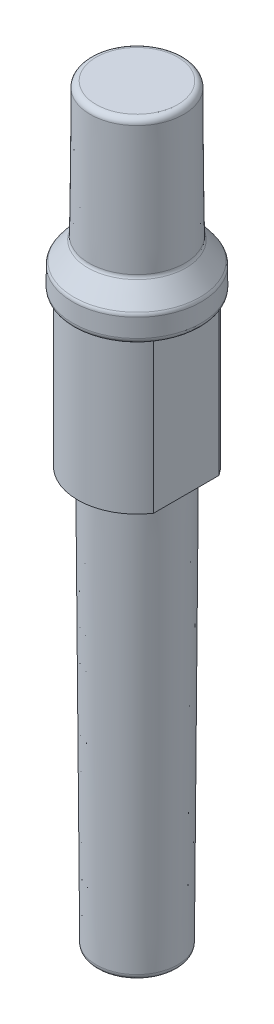
SolidWorks part; units mm, degrees
material "Polycarbonate (PC)"
ref_plane "Front Plane" through (0, 0, 0) normal (0, 0, 1) x (1, 0, 0)
ref_plane "Top Plane" through (0, 0, 0) normal (0, 1, 0) x (1, 0, 0)
ref_plane "Right Plane" through (0, 0, 0) normal (1, 0, 0) x (0, 0, -1)
sketch "Sketch1" plane through (0, 0, 0) normal (0, 1, 0) x (1, 0, 0)
  circle A0 centre (0, 0) radius 7.5
  dimension "D1" = 15
sketch "Sketch2" plane through (0, 0, 0) normal (0, 1, 0) x (1, 0, 0)
  line L0 (-8.5, 5.6383) -> (-8.5, -5.6383)
  line L1 (8.5, 5.6383) -> (8.5, -5.6383)
  line L2 (-8.5, 0) -> (8.5, 0) construction
  arc A0 (-8.5, -5.6383) -> (8.5, -5.6383) centre (0, 0) ccw
  arc A1 (8.5, 5.6383) -> (-8.5, 5.6383) centre (0, 0) ccw
  dimension "D1" = 20.4
  dimension "D2" = 17
ref_plane "Plane1" through (0, -72, 0) normal (0, 1, 0) x (1, 0, 0)
sketch "Sketch3" plane through (0, -72, 0) normal (0, 1, 0) x (1, 0, 0)
  circle A0 centre (0, 0) radius 7
  dimension "D1" = 14
loft "Loft1" add profiles "Sketch1", "Sketch3"
extrude "Boss-Extrude2" add sketch "Sketch2" along normal blind 25.85
sketch "Sketch8" plane through (0, 0, 0) normal (1, 0, 0) x (0, 0, -1)
  line L0 (10.2, 25.85) -> (5.6383, 25.85) construction
  line L1 (0, 25.85) -> (11.075, 25.85)
  line L2 (11.075, 25.85) -> (11.075, 30.35)
  line L3 (11.075, 30.35) -> (8.25, 34.05)
  line L4 (8.25, 34.05) -> (8.0454, 57.49)
  line L5 (8.0454, 57.49) -> (0, 57.49)
  line L6 (0, 57.49) -> (0, 25.85)
  point P0 (0, 25.85)
  dimension "D1" = 11.075
  dimension "D2" = 90
  dimension "D3" = 8.25
  dimension "D4" = 0.5
  dimension "D5" = 4.5
  dimension "D6" = 8.2
  dimension "D7" = 31.64
revolve "Revolve1" add sketch "Sketch8" angle 360 about L6
fillet "Fillet5" radius 1 6 edges at (0, 30.35, 11.075) (0, 34.05, 8.25) (0, 57.49, 8.0454) (0, 25.85, 11.075) (0, 0, 7.5) (0, -72, 7)
equation "\"g\"=1"
